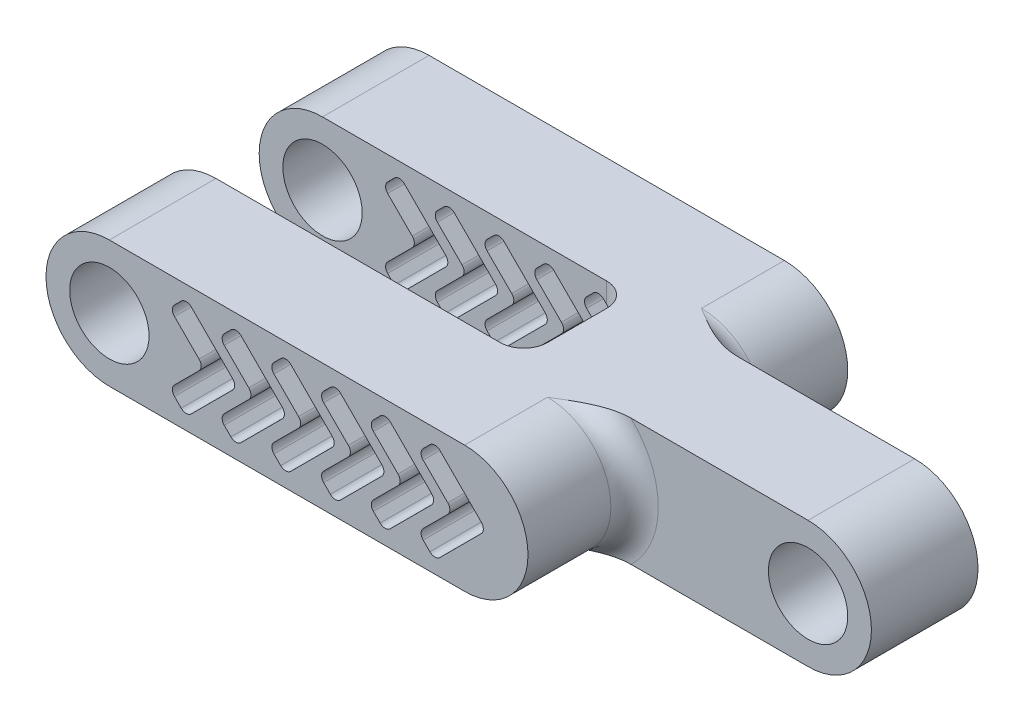
SolidWorks part; units mm, degrees
ref_plane "Front" through (0, 0, 0) normal (0, 0, 1) x (1, 0, 0)
ref_plane "Top" through (0, 0, 0) normal (0, 1, 0) x (1, 0, 0)
ref_plane "Right" through (0, 0, 0) normal (1, 0, 0) x (0, 0, -1)
sketch "Sketch1" plane through (0, 0, 0) normal (0, 0, 1) x (1, 0, 0)
  line L0 (0, 0) -> (15, 0) construction
  line L1 (0, 2.675) -> (15, 2.675)
  line L2 (0, -2.675) -> (15, -2.675)
  arc A0 (0, 2.675) -> (0, -2.675) centre (0, 0) ccw
  arc A1 (15, -2.675) -> (15, 2.675) centre (15, 0) ccw
  circle A2 centre (0, 0) radius 1.675
  circle A3 centre (5, 0) radius 1.675
  circle A5 centre (15, 0) radius 1.675
  circle A6 centre (10, 0) radius 1.675 [skipped]
  point P3 (7.5, 0)
  dimension "D1" = 3.35
  dimension "D2" = 1
  dimension "D3" = 15
  dimension "D4" = 4
extrude "Boss-Extrude1" add sketch "Sketch1" along normal mid plane 4.5
sketch "Sketch2" plane through (0, 0, 2.25) normal (0, 0, 1) x (1, 0, 0)
  line L0 (5, 0) -> (-10, 0) construction
  line L1 (5, -2.675) -> (-10, -2.675)
  line L2 (5, 2.675) -> (-10, 2.675)
  line L3 (15, 2.675) -> (0, 2.675) construction
  line L4 (0, -2.675) -> (15, -2.675) construction
  arc A0 (5, -2.675) -> (5, 2.675) centre (5, 0) ccw
  arc A1 (-10, 2.675) -> (-10, -2.675) centre (-10, 0) ccw
  circle A2 centre (5, 0) radius 1.675 construction
  circle A4 centre (-10, 0) radius 1.675
  circle A6 centre (15, 0) radius 1.675 construction
  point P3 (-2.5, 0)
  dimension "D1" = 15
extrude "Boss-Extrude2" add sketch "Sketch2" along normal blind 4.5 and the other way blind 9
sketch "Sketch3" plane through (0, 0, 0) normal (0, 0, 1) x (1, 0, 0)
  line L0 (5, 2.675) -> (-10, 2.675) construction
  line L1 (-12.675, 2.675) -> (3, 2.675)
  line L2 (-12.675, 2.675) -> (-12.675, -2.675)
  line L3 (-12.675, -2.675) -> (3, -2.675)
  line L4 (3, 2.675) -> (3, -2.675)
  line L5 (-10, -2.675) -> (5, -2.675) construction
  arc A0 (5, -2.675) -> (5, 2.675) centre (5, 0) ccw construction
  arc A3 (-10, 2.675) -> (-10, -2.675) centre (-10, 0) ccw construction
  dimension "D1" = 2
extrude "Cut-Extrude3" cut sketch "Sketch3" against normal mid plane 4.5
sketch "Sketch4" plane through (0, 0, 6.75) normal (0, 0, 1) x (1, 0, 0)
  line L0 (-6.9672, 1.9571) -> (-7.25, 1.6743)
  line L1 (-7.25, 1.25) -> (-6.2121, 0.2121)
  line L2 (-6.2121, -0.2121) -> (-7.25, -1.25)
  line L3 (-7.25, -1.6743) -> (-6.9672, -1.9571)
  line L4 (-6.5429, -1.9571) -> (-4.7979, -0.2121)
  line L5 (-4.7979, 0.2121) -> (-6.5429, 1.9571)
  line L6 (0, 0) -> (-7.7232, 0) construction
  circle A0 centre (-10, 0) radius 1.675 construction
  arc A1 (-6.9672, -1.9571) -> (-6.5429, -1.9571) centre (-6.755, -1.745) ccw
  arc A2 (-7.25, -1.25) -> (-7.25, -1.6743) centre (-7.0379, -1.4621) ccw
  arc A3 (-6.2121, 0.2121) -> (-6.2121, -0.2121) centre (-6.4243, 0) cw
  arc A4 (-4.7979, -0.2121) -> (-4.7979, 0.2121) centre (-5.0101, 0) ccw
  arc A5 (-7.25, 1.6743) -> (-7.25, 1.25) centre (-7.0379, 1.4621) ccw
  arc A6 (-6.9672, 1.9571) -> (-6.5429, 1.9571) centre (-6.755, 1.745) cw
  point P9 (-5.5912, 0.2121)
  point P10 (-4.5648, 0.2121)
  point P11 (-7.6476, -1.6476)
  point P23 (-7.4621, -1.4621)
  point P26 (-6, 0)
  point P29 (-4.5858, 0)
  dimension "D4" = 0.3
  dimension "D1" = 1
  dimension "D2" = 2.75
  dimension "D3" = 4
extrude "Cut-Extrude2" cut sketch "Sketch4" against normal through all both and the other way through all
pattern_linear "LPattern1" count 6 spacing 2.1 along (1, 0, 0) of "Cut-Extrude2"
fillet "Fillet1" radius 1 6 edges at (7.675, 0, -2.25) (7.675, 0, 2.25) (3, -1.7446, 2.25) (3, -1.7446, -2.25) (3, 1.7446, -2.25) (3, 1.7446, 2.25)
